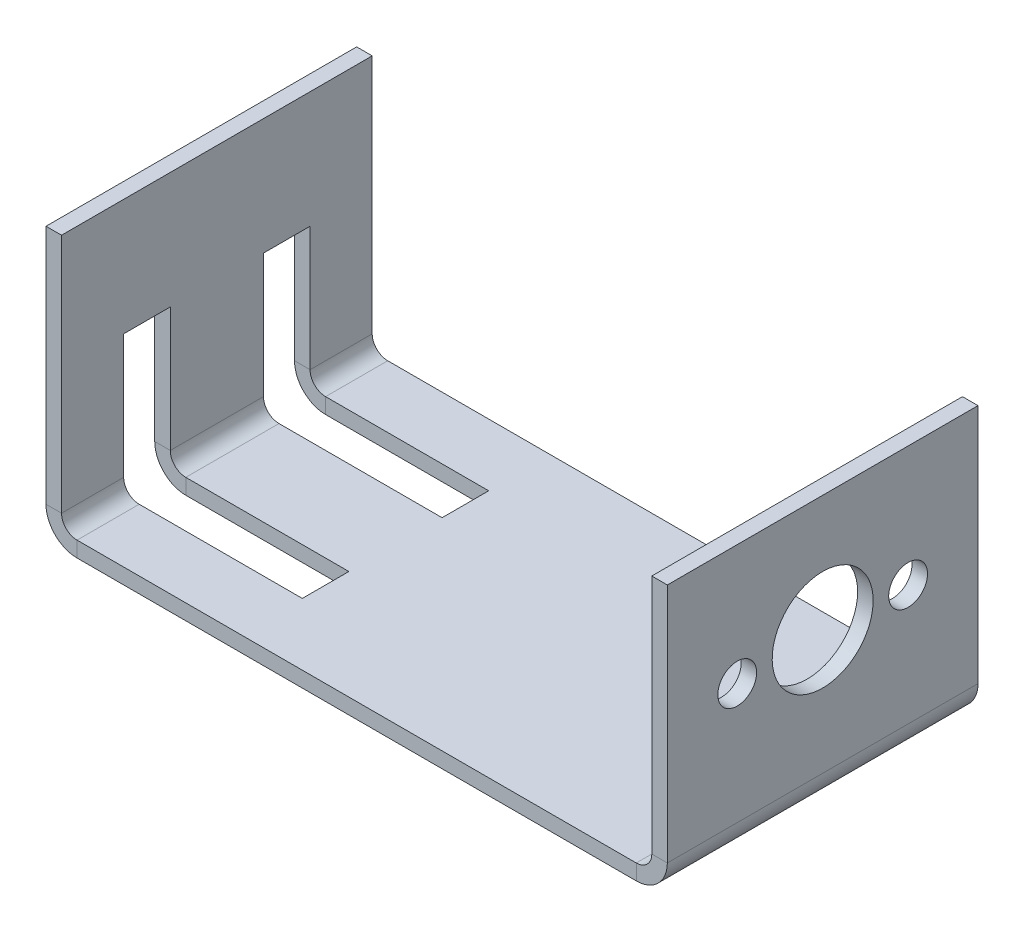
SolidWorks part; units mm, degrees
note: The reader was unsure of these and kept them because the rebuilt part matched: flange length of "Edge-Flange1".
ref_plane "Front Plane" through (0, 0, 0) normal (0, 0, 1) x (1, 0, 0)
ref_plane "Top Plane" through (0, 0, 0) normal (0, 1, 0) x (1, 0, 0)
ref_plane "Right Plane" through (0, 0, 0) normal (1, 0, 0) x (0, 0, -1)
sketch "Sketch1" plane through (0, 0, 0) normal (0, 1, 0) x (1, 0, 0)
  line L1 (-40, 20) -> (40, 20)
  line L2 (-40, 20) -> (-40, -20)
  line L3 (-40, -20) -> (40, -20)
  line L4 (40, 20) -> (40, -20)
  line L5 (-40, 20) -> (40, -20) construction
  line L6 (-40, -20) -> (40, 20) construction
  point P0 (0, 0)
base flange "Base-Flange1" sketch "Sketch1" thickness 2 reverse thickness direction no parameters "D1"=0.7366
edge flange "Edge-Flange1" sketch "Sketch10" flange profiles "Sketch10", "Sketch11" flange angle 90 flange length 35 flange position material inside bend radius 2 thickness 2 relief rectangular parameters "D6"=10, "D8"=0.5
sketch "Sketch10" plane through (40, 0, 0) normal (1, 0, 0) x (0, 0, -1)
  line L2 (-20, 0) -> (-20, 33)
  line L3 (-20, 33) -> (20, 33)
  line L4 (20, 33) -> (20, 0)
  line L15 (-20, 0) -> (20, 0) construction
  line L16 (-20, 0) -> (20, 0)
sketch "Sketch11" plane through (-40, 0, 0) normal (-1, 0, 0) x (0, 0, 1)
  line L2 (-20, 0) -> (-20, 33)
  line L3 (-20, 33) -> (20, 33)
  line L4 (20, 33) -> (20, 0)
  line L11 (-20, 0) -> (20, 0) construction
  line L12 (-20, 0) -> (20, 0)
bend "EdgeBend1" bend radius 2 bend angle 90 parameters "D5"=1
bend "EdgeBend2" bend radius 2 bend angle 90 parameters "D5"=2
sketch "Sketch14" plane through (40, 0, 0) normal (1, 0, 0) x (0, 0, -1)
  line L0 (20, -2) -> (-20, -2) construction
  line L1 (20, 2) -> (20, 33) construction
  line L2 (0, 19.25) -> (0, -19.25) construction
  circle A0 centre (0, 18) radius 6.5
  circle A1 centre (11, 17.5) radius 2.5
  circle A2 centre (-11, 17.5) radius 2.5
  dimension "D1" = 20
  dimension "D2" = 20
  dimension "D3" = 11
extrude "Cut-Extrude1" cut sketch "Sketch14" against normal blind 10 normal cut yes
sketch "Sketch15" plane through (-40, 0, 0) normal (-1, 0, 0) x (0, 0, 1)
  line L0 (20, 2) -> (-20, 2) construction
  line L1 (-12, -14) -> (-6, -14)
  line L2 (-12, -14) -> (-12, 18)
  line L3 (-12, 18) -> (-6, 18)
  line L4 (-6, -14) -> (-6, 18)
  line L5 (-12, -14) -> (-6, 18) construction
  line L6 (-12, 18) -> (-6, -14) construction
  line L7 (20, 33) -> (-20, 33) construction
  line L12 (0, -26.9883) -> (0, 26.9883) construction
  line L13 (12, 18) -> (6, 18)
  line L14 (12, 18) -> (6, -14) construction
  line L15 (12, -14) -> (6, 18) construction
  line L16 (6, -14) -> (6, 18)
  line L17 (12, -14) -> (12, 18)
  line L18 (12, -14) -> (6, -14)
  point P0 (-9, 2)
  point P7 (7.1843, 2)
  point P12 (-9, 18)
  dimension "D1" = 6
  dimension "D2" = 6
  dimension "D3" = 15
extrude "Cut-Extrude2" cut sketch "Sketch15" against normal blind 25 normal cut yes
sketch "Bend-Lines1" [suppressed] plane through (0, 0, 0) normal (0, 1, 0) x (1, 0, 0)
sketch "Bounding-Box1" [suppressed] plane through (0, 0, 0) normal (0, 1, 0) x (1, 0, 0)
sheet metal parameters "Sheet-Metal1" thickness 2 parameters "D1"=0.7366
flat pattern "Flat-Pattern1" [suppressed]
sketch "Bend-Lines2" plane through (0, 0, 0) normal (0, 1, 0) x (1, 0, 0)
sketch3d "Bounding-Box2" [suppressed]
  line L0 (-40, -20, 0) -> (40, -20, 0) construction
  line L1 (-40, 20, 0) -> (40, 20, 0) construction
  line L2 (-40, -20, 0) -> (-40, 20, 0) construction
  line L3 (40, -20, 0) -> (40, 20, 0) construction
sheet metal parameters "Sheet-Metal2" thickness 2 parameters "D1"=0.7366
flat pattern "Flat-Pattern1"
sketch "Bend-Lines2" plane through (0, 0, 0) normal (0, 1, 0) x (1, 0, 0)
  line L0 (-38.3562, 20) -> (-38.3562, -20) construction
  line L1 (38.3562, -20) -> (38.3562, 20) construction
  line L2 (-38.3562, 20) -> (-38.3562, -20) construction
  line L3 (38.3562, -20) -> (38.3562, 20) construction
sketch3d "Bounding-Box2" [suppressed]
  line L0 (71.7124, -20, 0) -> (-71.7124, -20, 0) construction
  line L1 (71.7124, 20, 0) -> (-71.7124, 20, 0) construction
  line L2 (71.7124, -20, 0) -> (71.7124, 20, 0) construction
  line L3 (-71.7124, -20, 0) -> (-71.7124, 20, 0) construction
bend of the flat pattern "Flatten-<EdgeBend1>1"
bend of the flat pattern "Flatten-<EdgeBend2>1"
sheet metal parameters "Sheet-Metal3" thickness 2 parameters "D1"=0.7366
flat pattern "Flat-Pattern1"
sketch "Bend-Lines2" plane through (0, 0, 0) normal (0, 1, 0) x (1, 0, 0)
  line L0 (-38.3562, 20) -> (-38.3562, -20) construction
  line L1 (38.3562, -20) -> (38.3562, 20) construction
  line L2 (-38.3562, 20) -> (-38.3562, -20) construction
  line L3 (38.3562, -20) -> (38.3562, 20) construction
sketch3d "Bounding-Box2" [suppressed]
  line L0 (71.7124, -20, 0) -> (-71.7124, -20, 0) construction
  line L1 (71.7124, 20, 0) -> (-71.7124, 20, 0) construction
  line L2 (71.7124, -20, 0) -> (71.7124, 20, 0) construction
  line L3 (-71.7124, -20, 0) -> (-71.7124, 20, 0) construction
bend of the flat pattern "Flatten-<EdgeBend1>1"
bend of the flat pattern "Flatten-<EdgeBend2>1"
sheet metal parameters "Sheet-Metal4" thickness 2 parameters "D1"=0.7366
flat pattern "Flat-Pattern1"
sketch "Bend-Lines2" plane through (0, 0, 0) normal (0, 1, 0) x (1, 0, 0)
  line L0 (-38.3562, -12) -> (-38.3562, -20) construction
  line L1 (38.3562, -20) -> (38.3562, 20) construction
  line L2 (-38.3562, -12) -> (-38.3562, -20) construction
  line L3 (38.3562, -20) -> (38.3562, 20) construction
  line L4 (-38.3562, 20) -> (-38.3562, 12) construction
  line L5 (-38.3562, 6) -> (-38.3562, -6) construction
sketch3d "Bounding-Box2" [suppressed]
  line L0 (71.7124, -20, 0) -> (-71.7124, -20, 0) construction
  line L1 (71.7124, 20, 0) -> (-71.7124, 20, 0) construction
  line L2 (71.7124, -20, 0) -> (71.7124, 20, 0) construction
  line L3 (-71.7124, -20, 0) -> (-71.7124, 20, 0) construction
bend of the flat pattern "Flatten-<EdgeBend1>1"
bend of the flat pattern "Flatten-<EdgeBend2>1"
